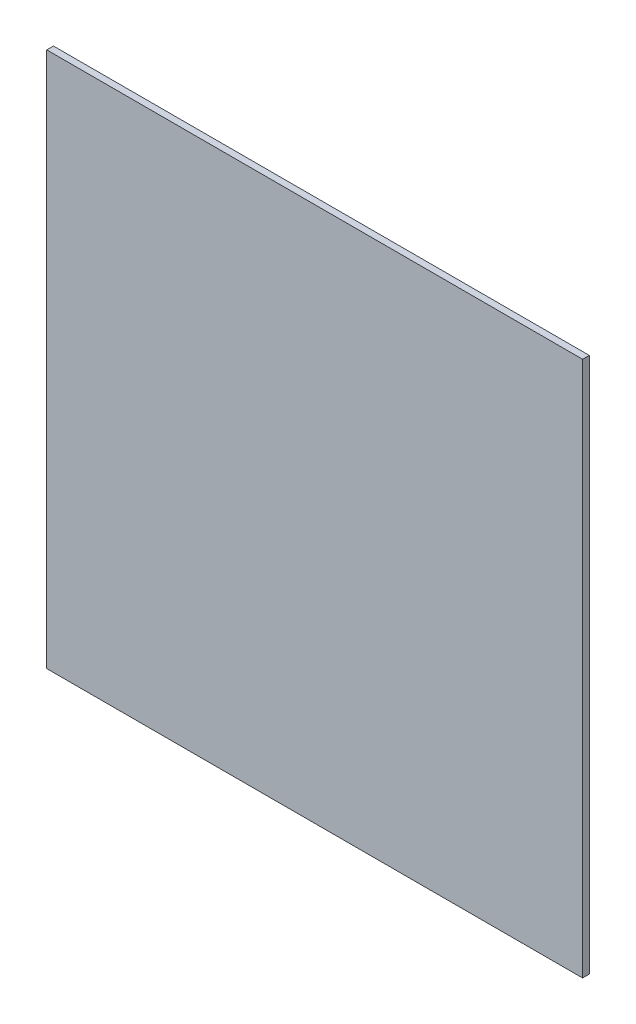
SolidWorks part; units mm, degrees
ref_plane "Ebene vorne" through (0, 0, 0) normal (0, 0, 1) x (1, 0, 0)
ref_plane "Ebene oben" through (0, 0, 0) normal (0, 1, 0) x (1, 0, 0)
ref_plane "Ebene rechts" through (0, 0, 0) normal (1, 0, 0) x (0, 0, -1)
sketch "Skizze1" plane through (0, 0, 0) normal (0, 0, 1) x (1, 0, 0)
  line L1 (400, -400) -> (-400, -400)
  line L2 (400, -400) -> (400, 400)
  line L3 (400, 400) -> (-400, 400)
  line L4 (-400, -400) -> (-400, 400)
  line L5 (400, -400) -> (-400, 400) construction
  line L6 (400, 400) -> (-400, -400) construction
  point P0 (0, 0)
  dimension "D1" = 800
  dimension "D2" = 800
extrude "Aufsatz-Linear austragen1" add sketch "Skizze1" along normal blind 10
